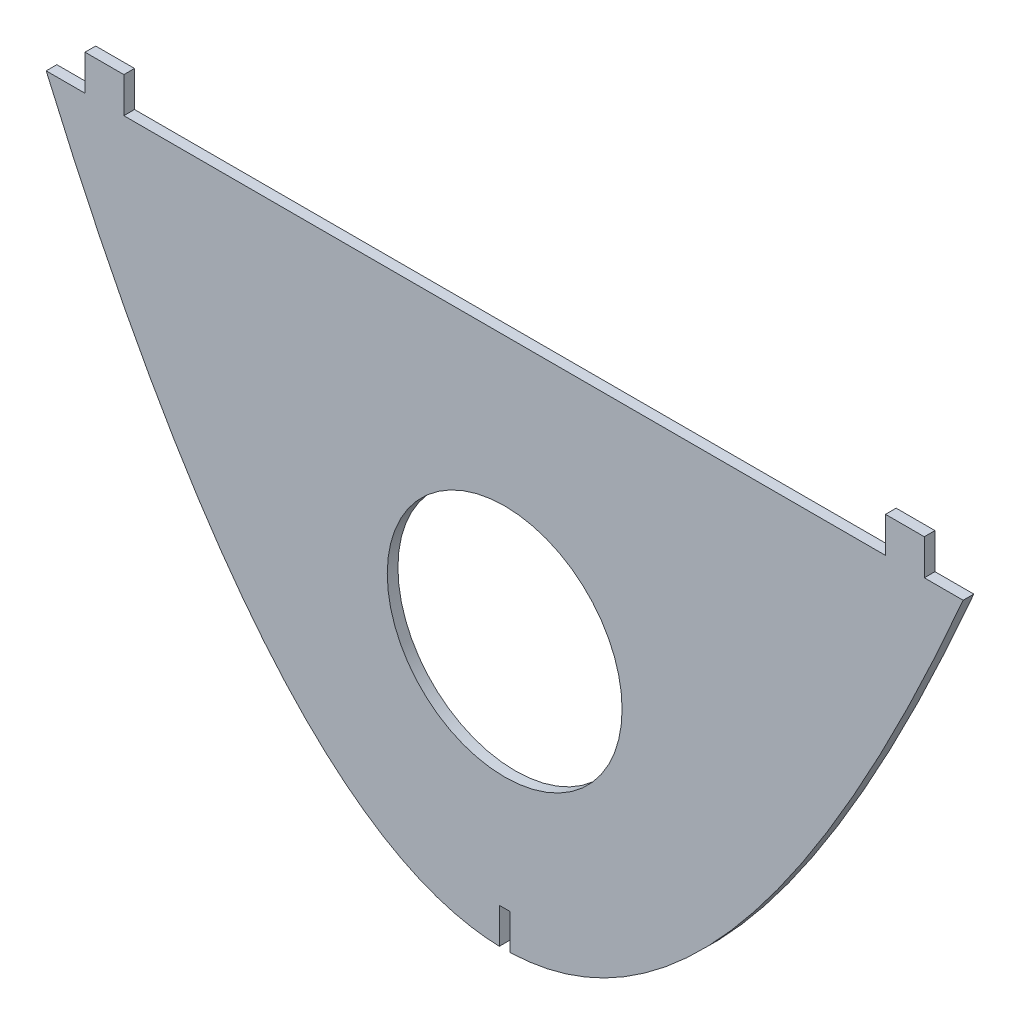
SolidWorks part; units mm, degrees
ref_plane "Front Plane" through (0, 0, 0) normal (0, 0, 1) x (1, 0, 0)
ref_plane "Top Plane" through (0, 0, 0) normal (0, 1, 0) x (1, 0, 0)
ref_plane "Right Plane" through (0, 0, 0) normal (1, 0, 0) x (0, 0, -1)
sketch "Sketch1" plane through (0, 0, 0) normal (0, 0, 1) x (1, 0, 0)
  line L2 (117.9381, 112.0276) -> (128.8518, 112.0276)
  line L3 (118.1892, 112.0276) -> (129.0994, 112.0276) construction
  line L4 (-117.9381, 112.0276) -> (-128.8518, 112.0276)
  line L5 (-117.9381, 112.0276) -> (-117.9381, 122.0276)
  line L6 (-117.9381, 122.0276) -> (-107.0244, 122.0276)
  line L7 (-107.0244, 122.0276) -> (-107.0244, 112.0276)
  line L8 (117.9381, 112.0276) -> (117.9381, 122.0276)
  line L9 (117.9381, 122.0276) -> (107.0244, 122.0276)
  line L10 (107.0244, 122.0276) -> (107.0244, 112.0276)
  line L11 (-107.0244, 112.0276) -> (107.0244, 112.0276)
  spline S0 degree 2 poles (-221.8965, 405.7451) (0, -480.5402) (221.8965, 405.7451) knots 0 0 0 1 1 1 construction
  spline S1 degree 2 poles (-128.8518, 112.0276) (0, -186.8226) (128.8518, 112.0276) knots 0.209658 0.209658 0.209658 0.790342 0.790342 0.790342
extrude "Boss-Extrude1" add sketch "Sketch1" along normal blind 3
sketch "Sketch2" plane through (0, 0, 0) normal (0, 0, 1) x (1, 0, 0)
  line L0 (0, -37.3975) -> (-1.5, -37.3975)
  line L1 (-1.5, -37.3975) -> (-1.5, -27.3975)
  line L2 (-1.5, -27.3975) -> (1.5, -27.3975)
  line L3 (1.5, -27.3975) -> (1.5, -37.3975)
  line L4 (1.5, -37.3975) -> (0, -37.3975)
  parabola Q0 (-128.8518, 112.0276) -> (128.8518, 112.0276) focus (0, -9.6198) apex (0, -37.3975) construction
  dimension "D1" = 1.5
  dimension "D2" = 1.5
  dimension "D3" = 10
extrude "Cut-Extrude1" cut sketch "Sketch2" against normal through all and the other way through all
sketch "Sketch3" plane through (0, 0, 0) normal (0, 0, 1) x (1, 0, 0)
  circle A0 centre (0, 37.563) radius 33
  dimension "D1" = 66
extrude "Cut-Extrude3" cut sketch "Sketch3" against normal through all and the other way through all
